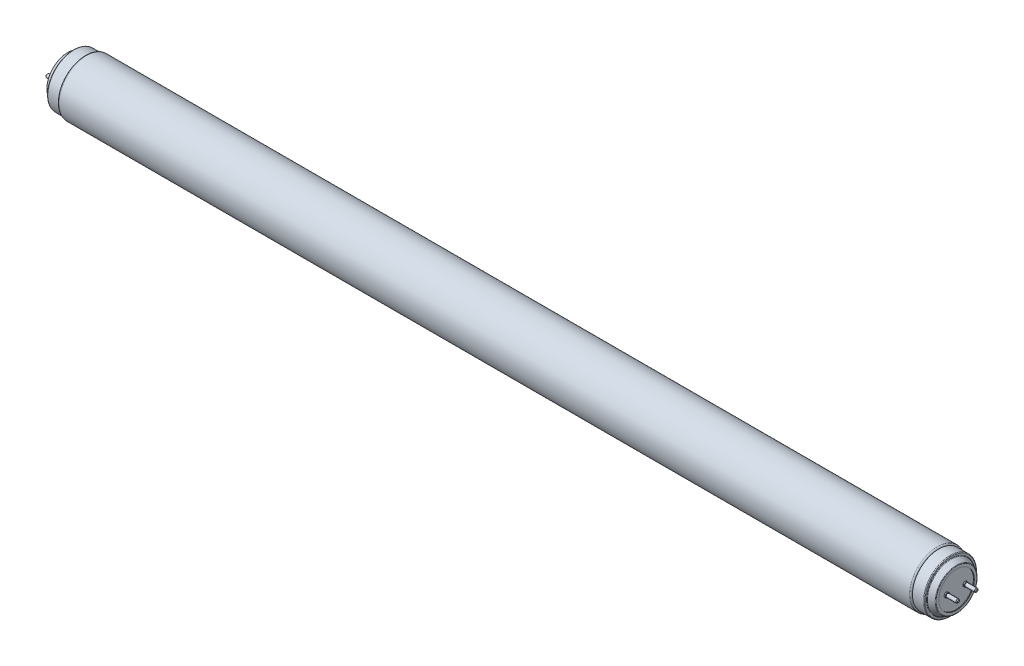
SolidWorks part; units mm, degrees
ref_plane "Front Plane" through (0, 0, 0) normal (0, 0, 1) x (1, 0, 0)
ref_plane "Top Plane" through (0, 0, 0) normal (0, 1, 0) x (1, 0, 0)
ref_plane "Right Plane" through (0, 0, 0) normal (1, 0, 0) x (0, 0, -1)
sketch "Sketch1" plane through (0, 0, 0) normal (0, 0, 1) x (1, 0, 0)
  line L0 (0, -17.75) -> (-7.5, -17.75)
  line L1 (-8, -17.25) -> (-8, -16.309)
  line L2 (-8.2764, -15.8618) -> (-11.7236, -14.1382)
  line L3 (-12, -13.691) -> (-12, -12)
  line L4 (-12, -12) -> (-11.5, -12)
  line L5 (-11.5, -12) -> (-11.5, 0)
  line L6 (-11.5, 0) -> (0, 0)
  line L7 (0, 0) -> (0, -17.75) construction
  line L8 (0.95, -18.7) -> (575.05, -18.7)
  line L9 (288, -18.7) -> (288, 0) construction
  line L10 (0, 0) -> (576, 0)
  line L11 (576, 0) -> (576, -17.75) construction
  line L12 (587.5, 0) -> (576, 0)
  line L13 (587.5, -12) -> (587.5, 0)
  line L14 (588, -12) -> (587.5, -12)
  line L15 (588, -13.691) -> (588, -12)
  line L16 (584.2764, -15.8618) -> (587.7236, -14.1382)
  line L17 (584, -17.25) -> (584, -16.309)
  line L18 (576, -17.75) -> (583.5, -17.75)
  line L19 (-11.5, 0) -> (-47.7314, 0) construction
  arc A0 (0, -17.75) -> (0.95, -18.7) centre (0.95, -17.75) ccw
  arc A1 (-7.5, -17.75) -> (-8, -17.25) centre (-7.5, -17.25) cw
  arc A2 (-8, -16.309) -> (-8.2764, -15.8618) centre (-8.5, -16.309) ccw
  arc A3 (-11.7236, -14.1382) -> (-12, -13.691) centre (-11.5, -13.691) cw
  arc A4 (587.7236, -14.1382) -> (588, -13.691) centre (587.5, -13.691) ccw
  arc A5 (584, -16.309) -> (584.2764, -15.8618) centre (584.5, -16.309) cw
  arc A6 (583.5, -17.75) -> (584, -17.25) centre (583.5, -17.25) ccw
  arc A7 (576, -17.75) -> (575.05, -18.7) centre (575.05, -17.75) cw
  point P15 (-8, -17.75)
  point P18 (-8, -16)
  point P21 (-12, -14)
  point P38 (588, -14)
  point P39 (584, -16)
  point P40 (584, -17.75)
  dimension "D9" = 0.5
  dimension "D1" = 17.75
  dimension "D2" = 8
  dimension "D3" = 14
  dimension "D4" = 12
  dimension "D5" = 0.5
  dimension "D6" = 12
  dimension "D7" = 16
  dimension "D8" = 18.7
  dimension "D10" = 600
revolve "Revolve1" add sketch "Sketch1" angle 360 about L19
sketch "Sketch2" plane through (-11.5, 0, 0) normal (-1, 0, 0) x (0, 0, 1)
  line L0 (-6.3, 0) -> (6.3, 0) construction
  circle A0 centre (-6.3, 0) radius 1.2
  circle A1 centre (6.3, 0) radius 1.2
  dimension "D1" = 2.4
  dimension "D2" = 15
extrude "Extrude1" add sketch "Sketch2" along normal blind 8
sketch "Sketch3" plane through (-11.5, 0, 0) normal (-1, 0, 0) x (0, 0, 1)
  circle A0 centre (-6.3, 0) radius 1.5
  circle A1 centre (6.3, 0) radius 1.5
  dimension "D1" = 3
  dimension "D2" = 3
extrude "Extrude2" add sketch "Sketch3" along normal blind 1
sketch "Sketch4" plane through (587.5, 0, 0) normal (1, 0, 0) x (0, 0, -1)
  circle A0 centre (6.3, 0) radius 1.2 construction
  circle A1 centre (-6.3, 0) radius 1.2 construction
  circle A2 centre (6.3, 0) radius 1.2
  circle A3 centre (-6.3, 0) radius 1.2
extrude "Extrude3" add sketch "Sketch4" along normal blind 8
sketch "Sketch5" plane through (587.5, 0, 0) normal (1, 0, 0) x (0, 0, -1)
  circle A0 centre (6.3, 0) radius 1.5 construction
  circle A1 centre (-6.3, 0) radius 1.5 construction
  circle A2 centre (6.3, 0) radius 1.5
  circle A3 centre (-6.3, 0) radius 1.5
extrude "Extrude4" add sketch "Sketch5" along normal blind 1
chamfer "Chamfer1" distance 0.3 angle 45 4 edges at (-12.5, 0, 7.8) (-12.5, 0, -4.8) (588.5, 0, -7.8) (588.5, 0, 4.8)
chamfer "Chamfer2" distance 0.5 angle 45 4 edges at (-19.5, 0, -5.1) (-19.5, 0, 7.5) (595.5, 0, -7.5) (595.5, 0, 5.1)
